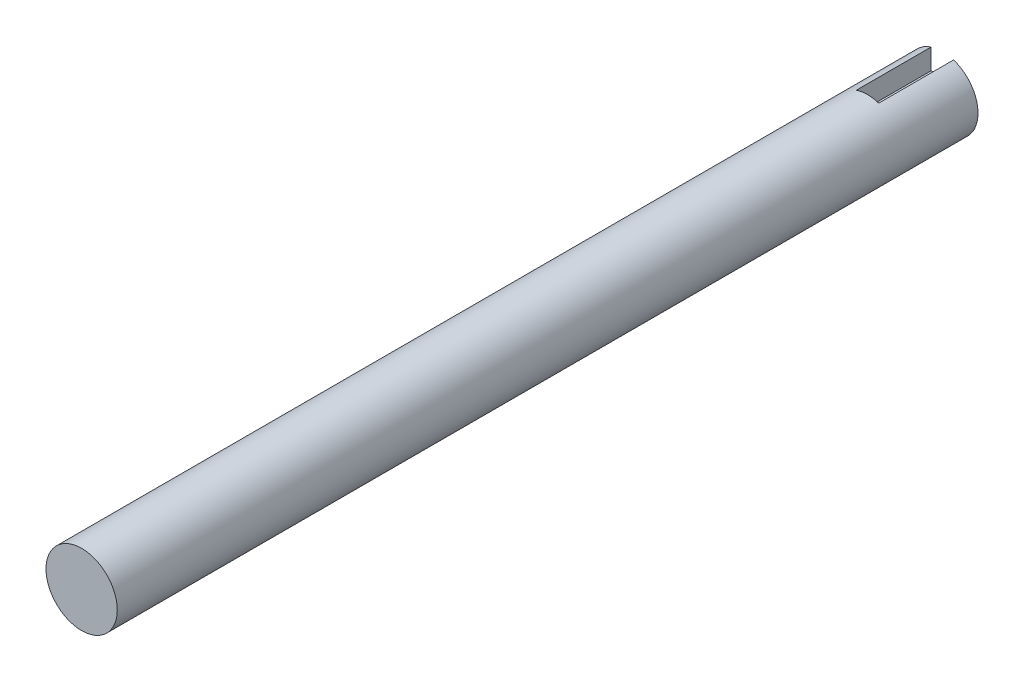
SolidWorks part; units mm, degrees
ref_plane "Front Plane" through (0, 0, 0) normal (0, 0, 1) x (1, 0, 0)
ref_plane "Top Plane" through (0, 0, 0) normal (0, 1, 0) x (1, 0, 0)
ref_plane "Right Plane" through (0, 0, 0) normal (1, 0, 0) x (0, 0, -1)
sketch "Sketch1" plane through (0, 0, 0) normal (0, 0, 1) x (1, 0, 0)
  line L1 (-1.5, 7.7625) -> (1.5, 7.7625)
  line L2 (-1.5, 7.7625) -> (-1.5, 1.7625)
  line L3 (-1.5, 1.7625) -> (1.5, 1.7625)
  line L4 (1.5, 7.7625) -> (1.5, 1.7625)
  line L5 (-1.5, 7.7625) -> (1.5, 1.7625) construction
  line L6 (-1.5, 1.7625) -> (1.5, 7.7625) construction
  circle A0 centre (0, 0) radius 4.7625
  point P3 (0, 4.7625)
  dimension "D1" = 9.525
  dimension "D2" = 3
  dimension "D3" = 3
extrude "Boss-Extrude1" add sketch "Sketch1" along normal blind 115 contours L2 A0 L4 L3 | L4 A0 L2 L3 region at (0, 3.2234, 0) region at (0, -0.4518, 0)
extrude "Cut-Extrude1" cut sketch "Sketch1<3>" along normal blind 10 contours L4 A0 L2 L3 region at (0, 3.2234, 0)
sketch "Sketch1<3>" plane through (0, 0, 0) normal (0, 0, 1) x (1, 0, 0) same geometry as "Sketch1"
